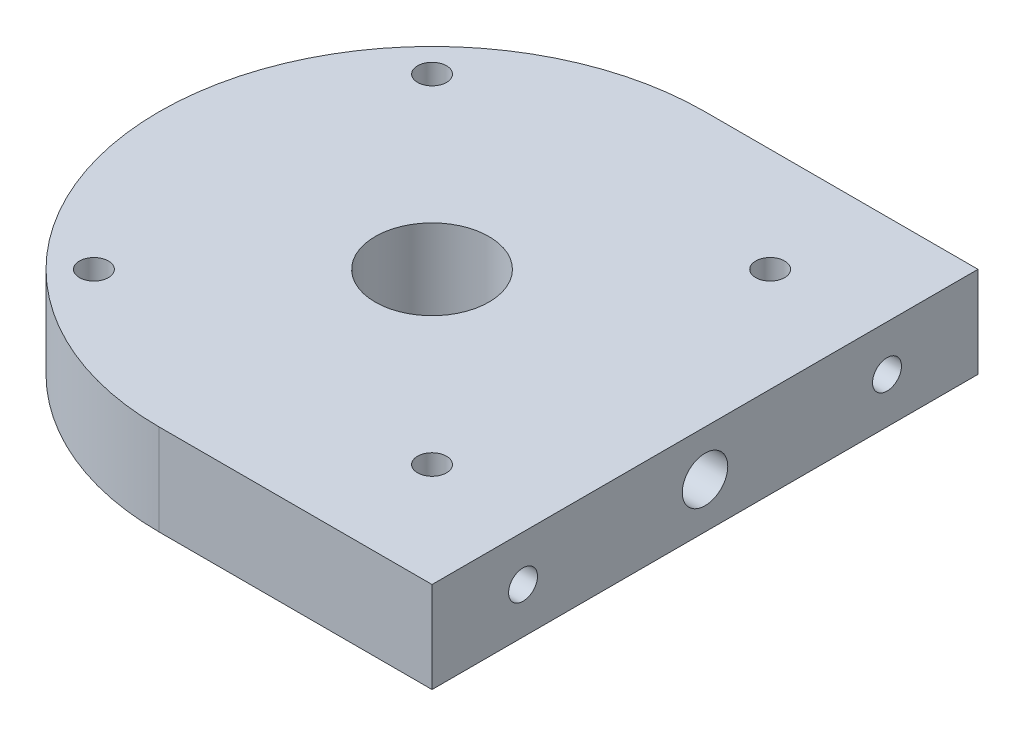
SolidWorks part; units mm, degrees
material "6061-T6 (SS)"
ref_plane "Front Plane" through (0, 0, 0) normal (0, 0, 1) x (1, 0, 0)
ref_plane "Top Plane" through (0, 0, 0) normal (0, 1, 0) x (1, 0, 0)
ref_plane "Right Plane" through (0, 0, 0) normal (1, 0, 0) x (0, 0, -1)
sketch "Sketch1" plane through (0, 0, 0) normal (0, 1, 0) x (1, 0, 0)
  line L1 (-38.1, -38.1) -> (38.1, -38.1)
  line L2 (-38.1, -38.1) -> (-38.1, 38.1)
  line L3 (-38.1, 38.1) -> (38.1, 38.1)
  line L4 (38.1, -38.1) -> (38.1, 38.1)
  line L5 (-38.1, -38.1) -> (38.1, 38.1) construction
  line L6 (-38.1, 38.1) -> (38.1, -38.1) construction
  point P0 (0, 0)
  dimension "D1" = 76.2
  dimension "D2" = 76.2
extrude "Boss-Extrude1" add sketch "Sketch1" along normal blind 12.7
sketch "Sketch2" plane through (38.1, 0, 0) normal (1, 0, 0) x (0, 0, -1)
  line L0 (-38.1, 0) -> (38.1, 0) construction
  point P0 (-25.4, 6.35)
  point P1 (25.4, 6.35)
  dimension "D1" = 25.4
  dimension "D2" = 25.4
  dimension "D3" = 6.35
hole_wizard "#10-32 Tapped Hole1" positions "Sketch4" profile "Sketch5" tap size "#10-32" standard "ANSI Inch"
sketch "Sketch4" plane through (38.1, 0, 0) normal (1, 0, 0) x (0, 0, -1)
  point P0 (-25.4, 6.35)
  point P3 (25.4, 6.35)
sketch "Sketch5" plane through (38.1, 6.35, 25.4) normal (0, 1, 0) x (0, 0, -1)
  line L0 (0, 0) -> (0, 10.8653)
  line L1 (0, 10.8653) -> (2.0193, 9.652)
  line L2 (2.0193, 9.652) -> (2.0193, 0)
  line L5 (2.0193, 0) -> (0, 0)
  line L10 (0, 10.8653) -> (-2.0193, 9.652) construction
  line L11 (0, -6.35) -> (0, 107.95) construction
  dimension "Tap Drill Dia." = 4.0386
  dimension "Tap Drill Depth" = 9.652
  dimension "Drill Angle" = 118
cosmetic thread "Hole Thread1" parameters "D1"=6.35, "D2"=4.826
cosmetic thread "Hole Thread2" parameters "D1"=6.35, "D2"=4.826
sketch "Sketch6" plane through (0, 12.7, 0) normal (0, 1, 0) x (1, 0, 0)
  line L1 (23.5966, 23.5966) -> (-23.5966, 23.5966) construction
  line L2 (23.5966, 23.5966) -> (23.5966, -23.5966) construction
  line L3 (23.5966, -23.5966) -> (-23.5966, -23.5966) construction
  line L4 (-23.5966, 23.5966) -> (-23.5966, -23.5966) construction
  line L5 (23.5966, 23.5966) -> (-23.5966, -23.5966) construction
  line L6 (23.5966, -23.5966) -> (-23.5966, 23.5966) construction
  circle A0 centre (-23.5966, 23.5966) radius 4.7625
  circle A1 centre (23.5966, 23.5966) radius 4.7625
  circle A2 centre (23.5966, -23.5966) radius 4.7625
  circle A3 centre (-23.5966, -23.5966) radius 4.7625
  point P0 (0, 0)
  point P7 (-23.5966, -23.5966)
  point P8 (-23.5966, 23.5966)
  point P9 (23.5966, 23.5966)
  point P10 (23.5966, -23.5966)
  dimension "D2" = 9.525
  dimension "D1" = 47.1932
hole_wizard "#10-32 Tapped Hole2" positions "Sketch8" profile "Sketch7" tap size "#10-32" standard "ANSI Inch" end condition through all
sketch "Sketch8" plane through (0, 12.7, 0) normal (0, 1, 0) x (1, 0, 0)
  point P0 (-23.5966, -23.5966)
  point P3 (-23.5966, 23.5966)
  point P6 (23.5966, 23.5966)
  point P9 (23.5966, -23.5966)
sketch "Sketch7" plane through (-23.5966, 12.7, 23.5966) normal (1, 0, 0) x (0, 0, 1)
  line L0 (0, 0) -> (0, 12.7)
  line L1 (0, 12.7) -> (2.0193, 12.7)
  line L2 (2.0193, 12.7) -> (2.0193, 0)
  line L5 (2.0193, 0) -> (0, 0)
  line L11 (0, -6.35) -> (0, 107.95) construction
  dimension "Thru Tap Drill Dia." = 4.0386
  dimension "Thru Tap Drill Depth" = 12.7
cosmetic thread "Hole Thread3" parameters "D2"=4.826
cosmetic thread "Hole Thread4" parameters "D2"=4.826
cosmetic thread "Hole Thread5" parameters "D2"=4.826
cosmetic thread "Hole Thread6" parameters "D2"=4.826
sketch "Sketch9" plane through (0, 12.7, 0) normal (0, 1, 0) x (1, 0, 0)
  circle A0 centre (0, 0) radius 7.9375
  dimension "D1" = 15.875
extrude "Cut-Extrude2" cut sketch "Sketch9" against normal through all
fillet "Fillet1" radius 38.1 2 edges at (-38.1, 6.35, -38.1) (-38.1, 6.35, 38.1)
sketch "Sketch10" plane through (0, 0, 0) normal (1, 0, 0) x (0, 0, -1)
  circle A0 centre (0, 6.35) radius 3.175
  dimension "D2" = 6.35
  dimension "D1" = 6.35
extrude "Cut-Extrude3" cut sketch "Sketch10" along normal through all
equation "\"D2@Sketch1\"=\"D1@Sketch1\""
